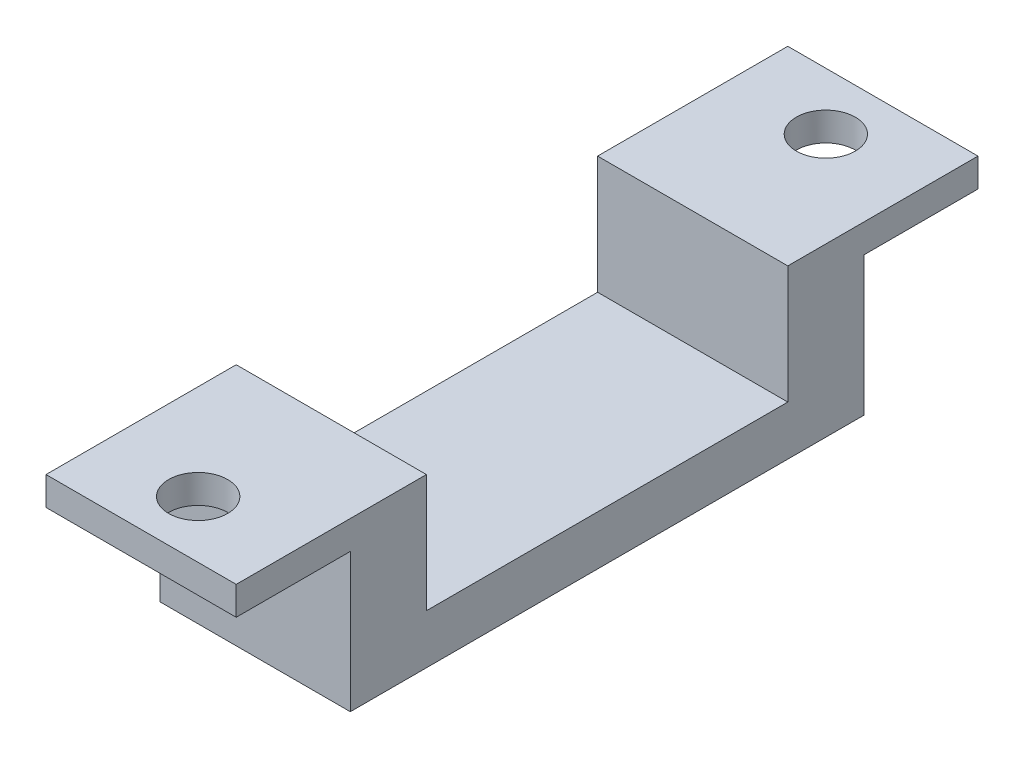
SolidWorks part; units mm, degrees
ref_plane "Alzado" through (0, 0, 0) normal (0, 0, 1) x (1, 0, 0)
ref_plane "Planta" through (0, 0, 0) normal (0, 1, 0) x (1, 0, 0)
ref_plane "Vista lateral" through (0, 0, 0) normal (1, 0, 0) x (0, 0, -1)
sketch "Croquis1" plane through (0, 0, 0) normal (0, 1, 0) x (1, 0, 0)
  line L0 (-22.8964, 0) -> (26.1311, 0) construction
  line L1 (-5, -13.5) -> (5, -13.5)
  line L2 (-5, -13.5) -> (-5, 13.5)
  line L3 (-5, 13.5) -> (5, 13.5)
  line L4 (5, -13.5) -> (5, 13.5)
  line L5 (-5, -13.5) -> (5, 13.5) construction
  line L6 (-5, 13.5) -> (5, -13.5) construction
  point P0 (0, 0)
  dimension "D1" = 27
  dimension "D2" = 10
extrude "Saliente-Extruir1" add sketch "Croquis1" along normal blind 2.6
sketch "Croquis2" plane through (0, 2.6, 0) normal (0, 1, 0) x (1, 0, 0)
  line L1 (-5, 9.5) -> (5, 9.5)
  line L2 (-5, 9.5) -> (-5, 13.5)
  line L3 (-5, 13.5) -> (5, 13.5)
  line L4 (5, 9.5) -> (5, 13.5)
  line L5 (-5, 9.5) -> (5, 13.5) construction
  line L6 (-5, 13.5) -> (5, 9.5) construction
  point P0 (0, 11.5)
  dimension "D1" = 4
extrude "Saliente-Extruir2" add sketch "Croquis2" along normal blind 6.2
sketch "Croquis3" plane through (0, 0, -13.5) normal (0, 0, -1) x (-1, 0, 0)
  line L1 (-5, 7.3) -> (5, 7.3)
  line L2 (-5, 7.3) -> (-5, 8.8)
  line L3 (-5, 8.8) -> (5, 8.8)
  line L4 (5, 7.3) -> (5, 8.8)
  line L5 (-5, 7.3) -> (5, 8.8) construction
  line L6 (-5, 8.8) -> (5, 7.3) construction
  line L7 (-5, 8.8) -> (5, 8.8) construction
  point P0 (0, 8.05)
  dimension "D1" = 1.5
  dimension "D2" = 10
extrude "Saliente-Extruir3" add sketch "Croquis3" along normal blind 6
sketch "Croquis4" plane through (0, 7.3, 0) normal (0, -1, 0) x (1, 0, 0)
  line L0 (5, -13.5) -> (-5, -13.5) construction
  circle A0 centre (0, -16.5) radius 1.55
  dimension "D1" = 3.1
  dimension "D2" = 3
extrude "Cortar-Extruir1" cut sketch "Croquis4" against normal blind 5 contours A0
mirror "Simetría1" about plane through (0, 0, 0) normal (0, 0, 1) of "Cortar-Extruir1", "Saliente-Extruir3", "Saliente-Extruir1", "Saliente-Extruir2"
